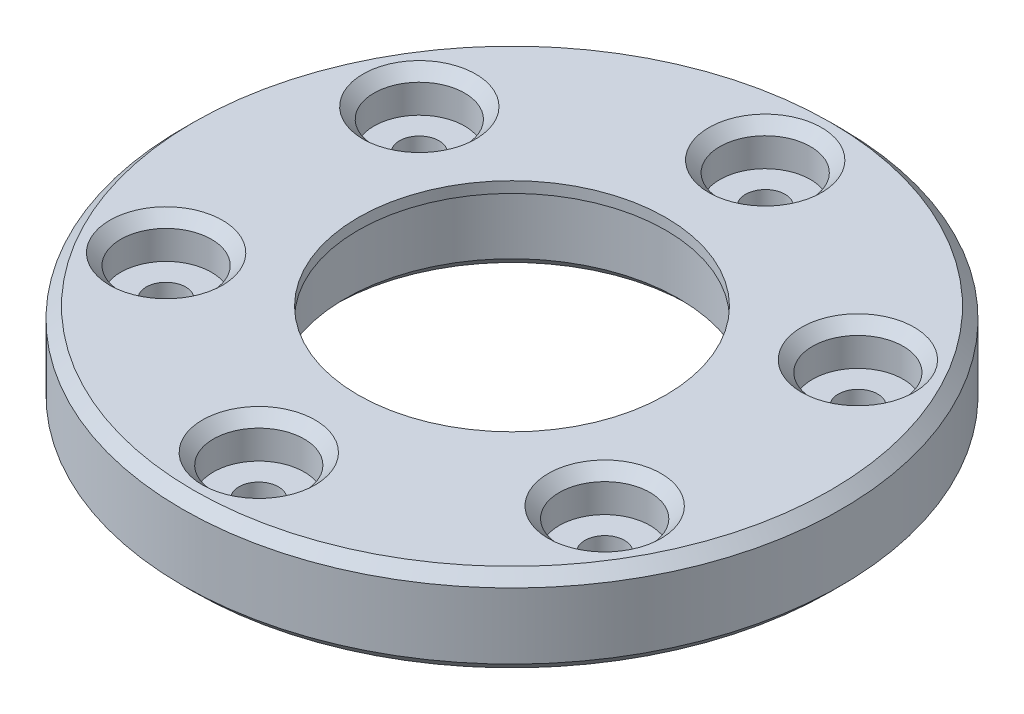
SolidWorks part; units mm, degrees
ref_plane "前视基准面" through (0, 0, 0) normal (0, 0, 1) x (1, 0, 0)
ref_plane "上视基准面" through (0, 0, 0) normal (0, 1, 0) x (1, 0, 0)
ref_plane "右视基准面" through (0, 0, 0) normal (1, 0, 0) x (0, 0, -1)
other "Configuration Table"
sketch "草图1" plane through (0, 0, 0) normal (0, 1, 0) x (1, 0, 0)
  circle A0 centre (0, 0) radius 7
  circle A1 centre (0, 0) radius 15
  circle A2 centre (0, 0) radius 11.525 construction
  circle A3 centre (0, 11.525) radius 2.065
  circle A4 centre (9.9809, 5.7625) radius 2.065
  circle A5 centre (9.9809, -5.7625) radius 2.065
  circle A6 centre (0, -11.525) radius 2.065
  circle A7 centre (-9.9809, -5.7625) radius 2.065
  circle A8 centre (-9.9809, 5.7625) radius 2.065
  point P19 (0, 0)
  dimension "D1" = 14
  dimension "D2" = 30
  dimension "D3" = 23.05
  dimension "D4" = 4.13
  dimension "D5" = 6
extrude "凸台-拉伸1" add sketch "草图1" along normal blind 1.8
sketch "草图2" plane through (0, 0, 0) normal (0, -1, 0) x (-1, 0, 0)
  circle A0 centre (0, 0) radius 7 construction
  circle A1 centre (0, 0) radius 15 construction
  circle A2 centre (0, 0) radius 7
  circle A3 centre (0, 0) radius 15
  circle A4 centre (0, 11.53) radius 0.9
  circle A6 centre (0, 0) radius 11.53 construction
  circle A7 centre (9.9853, 5.765) radius 0.9
  circle A8 centre (9.9853, -5.765) radius 0.9
  circle A9 centre (0, -11.53) radius 0.9
  circle A10 centre (-9.9853, -5.765) radius 0.9
  circle A11 centre (-9.9853, 5.765) radius 0.9
  point P21 (0, 0)
  dimension "D1" = 1.8
  dimension "D2" = 23.06
  dimension "D3" = 6
extrude "凸台-拉伸2" add sketch "草图2" along normal blind 2.2
sketch "草图3" plane through (0, -2.2, 0) normal (0, -1, 0) x (-1, 0, 0)
  circle A0 centre (0, 0) radius 7.6
  dimension "D1" = 15.2
extrude "切除-拉伸1" cut sketch "草图3" against normal blind 3.5
chamfer "倒角1" distance 0.5 angle 45 15 edges at (0, -2.2, -15) (-9.9809, 1.8, -3.6975) (0, 1.8, 13.59) (9.9809, 1.8, -3.6975) (0, 1.8, 15) (0, 1.8, -9.46) (9.9809, 1.8, 7.8275) (-9.9809, 1.8, 7.8275) (9.9853, -2.2, -6.665) (0, -2.2, 10.63) (-9.9853, -2.2, -6.665) (0, -2.2, -12.43) (-9.9853, -2.2, 4.865) (9.9853, -2.2, 4.865) (0, -2.2, -7.6)
